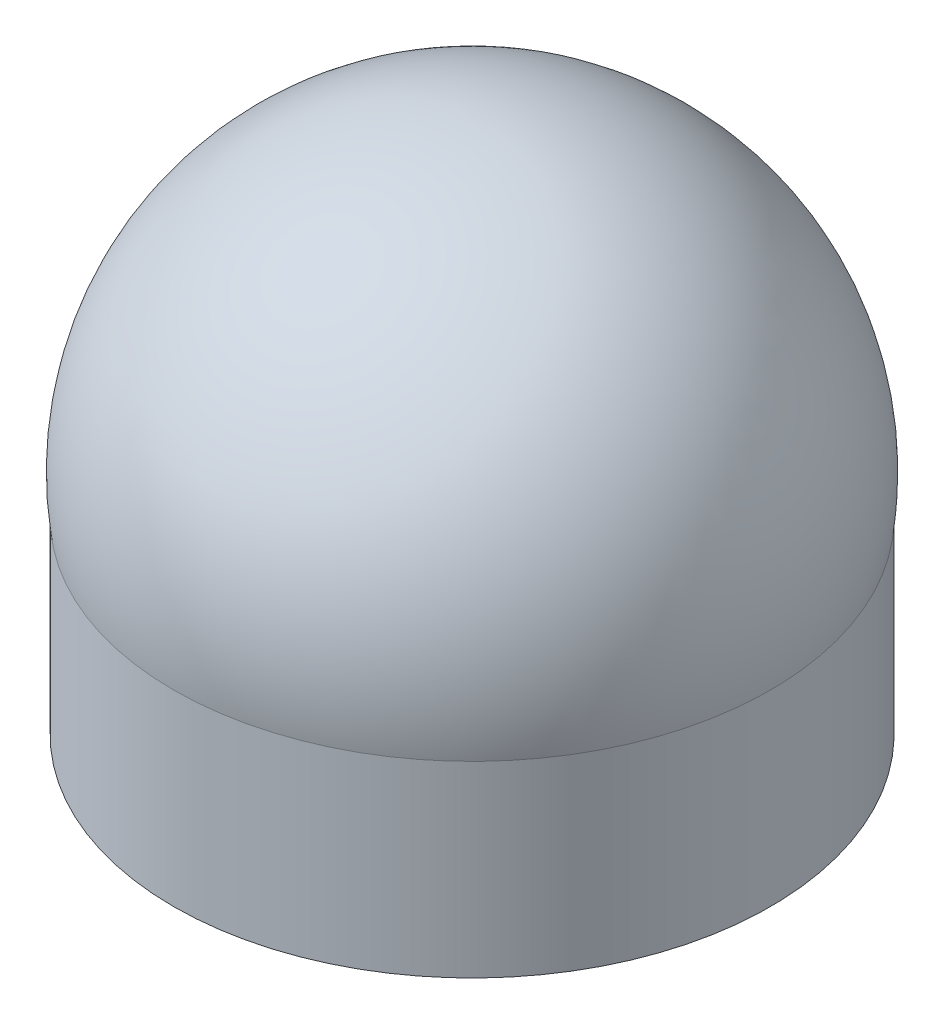
SolidWorks part; units mm, degrees
ref_plane "前视基准面" through (0, 0, 0) normal (0, 0, 1) x (1, 0, 0)
ref_plane "上视基准面" through (0, 0, 0) normal (0, 1, 0) x (1, 0, 0)
ref_plane "右视基准面" through (0, 0, 0) normal (1, 0, 0) x (0, 0, -1)
sketch "草图1" plane through (0, 0, 0) normal (0, 1, 0) x (1, 0, 0)
  circle A0 centre (0, 0) radius 8.75
  dimension "D1" = 17.5
extrude "凸台-拉伸1" add sketch "草图1" along normal blind 5.5
dome "圆顶1" faces to dome 1 distance 10 reverse direction no elliptical dome no face at (0, 5.5, 8.75) parameters "D1"=10
shell "抽壳1" thickness 2 removed face at (0, 0, 8.75)
